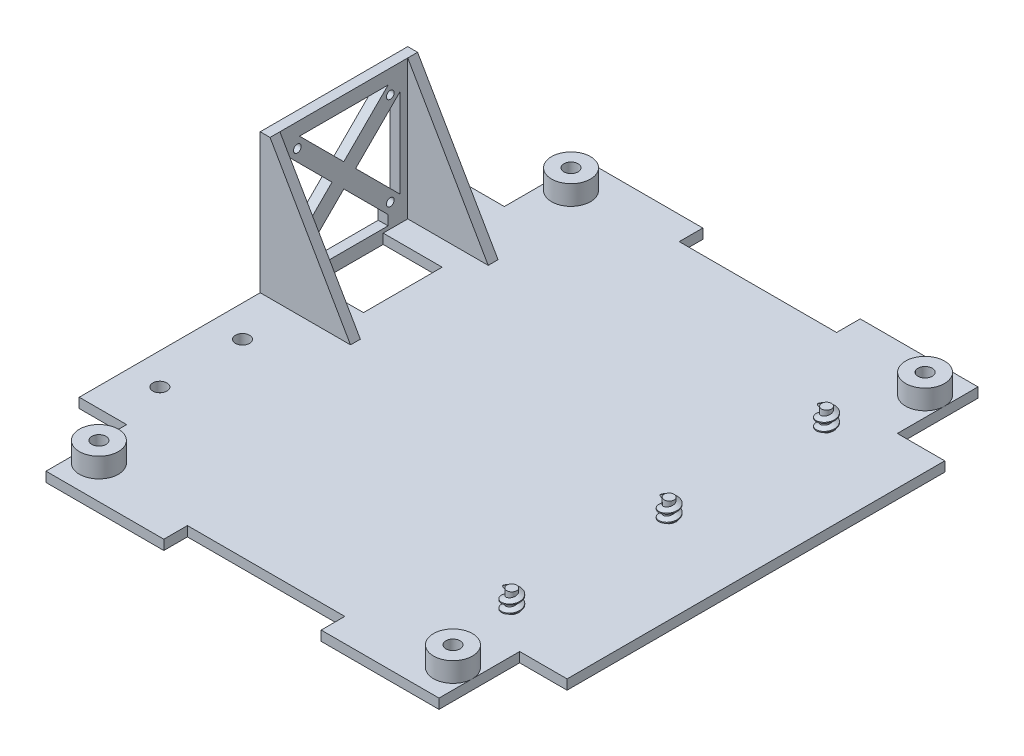
SolidWorks part; units mm, degrees
ref_plane "Front Plane" through (0, 0, 0) normal (0, 0, 1) x (1, 0, 0)
ref_plane "Top Plane" through (0, 0, 0) normal (0, 1, 0) x (1, 0, 0)
ref_plane "Right Plane" through (0, 0, 0) normal (1, 0, 0) x (0, 0, -1)
sketch "Sketch1" plane through (0, 0, 0) normal (0, 1, 0) x (1, 0, 0)
  line L0 (-25.4, 86.995) -> (-63.4314, 86.995)
  line L1 (-88.9, -101.6) -> (88.9, -101.6) construction
  line L2 (101.6, -88.9) -> (101.6, 88.9) construction
  line L3 (88.9, 101.6) -> (-88.9, 101.6) construction
  line L4 (-78.74, -60.96) -> (-63.4314, -60.96)
  line L5 (-63.4314, -60.96) -> (-63.4314, -86.995)
  line L6 (-63.4314, -86.995) -> (-25.4, -86.995)
  line L7 (63.4314, -86.995) -> (63.4314, -60.96)
  line L8 (63.4314, -60.96) -> (78.74, -60.96)
  line L9 (78.74, -60.96) -> (78.74, -25.4)
  line L10 (78.74, 60.96) -> (63.4314, 60.96)
  line L11 (63.4314, 60.96) -> (63.4314, 86.995)
  line L12 (63.4314, 86.995) -> (25.4, 86.995)
  line L13 (-63.4314, 86.995) -> (-63.4314, 60.96)
  line L14 (-63.4314, 60.96) -> (-78.74, 60.96)
  line L15 (-78.74, 60.96) -> (-78.74, 25.4)
  line L16 (-78.74, -25.4) -> (-78.74, -60.96)
  line L17 (-78.74, -25.4) -> (-71.12, -25.4)
  line L19 (-78.74, 25.4) -> (-71.12, 25.4)
  line L20 (-71.12, -25.4) -> (-71.12, 25.4)
  line L22 (-25.4, 86.995) -> (-25.4, 79.375)
  line L23 (-25.4, 79.375) -> (25.4, 79.375)
  line L24 (25.4, 86.995) -> (25.4, 79.375)
  line L25 (78.74, 25.4) -> (71.12, 25.4)
  line L27 (78.74, -25.4) -> (71.12, -25.4)
  line L28 (71.12, 25.4) -> (71.12, -25.4)
  line L30 (25.4, -86.995) -> (25.4, -79.375)
  line L31 (25.4, -79.375) -> (-25.4, -79.375)
  line L32 (-25.4, -86.995) -> (-25.4, -79.375)
  line L33 (78.74, 25.4) -> (78.74, 60.96)
  line L34 (25.4, -86.995) -> (63.4314, -86.995)
  line L35 (-101.6, 88.9) -> (-101.6, -88.9) construction
  arc A0 (88.9, -101.6) -> (101.6, -88.9) centre (88.9, -88.9) ccw construction
  arc A1 (-101.6, -88.9) -> (-88.9, -101.6) centre (-88.9, -88.9) ccw construction
  arc A2 (101.6, 88.9) -> (88.9, 101.6) centre (88.9, 88.9) ccw construction
  arc A3 (-101.6, 88.9) -> (-88.9, 101.6) centre (-88.9, 88.9) cw construction
  circle A4 centre (-57.15, 76.2) radius 2.286
  circle A5 centre (57.15, 76.2) radius 2.286
  circle A6 centre (57.15, -76.2) radius 2.286
  circle A7 centre (-57.15, -76.2) radius 2.286
  point P3 (0, 101.6)
  point P5 (101.6, 0)
  point P13 (101.6, 101.6)
  point P16 (-101.6, 101.6)
  point P38 (-71.12, 0)
  point P55 (0, -79.375)
  point P56 (0, 79.375)
  point P57 (71.12, 0)
  dimension "D2" = 12.7
  dimension "D11" = 4.572
  dimension "D8" = 44.45
  dimension "D1" = 203.2
  dimension "D3" = 203.2
  dimension "D4" = 22.86
  dimension "D5" = 15.3086
  dimension "D6" = 35.56
  dimension "D7" = 173.99
  dimension "D12" = 50.8
  dimension "D13" = 25.4
  dimension "D14" = 44.45
  dimension "D15" = 25.4
  dimension "D18" = 7.62
extrude "Main Body" add sketch "Sketch1" along normal blind 3.175
sketch "Sketch34" plane through (0, 3.175, 0) normal (0, 1, 0) x (1, 0, 0)
  line L0 (78.74, 25.4) -> (78.74, -25.4)
  line L1 (-78.74, 25.4) -> (-78.74, -25.4)
  line L28 (-78.74, -25.4) -> (-78.74, -60.96)
  line L29 (-78.74, -60.96) -> (-63.4314, -60.96)
  line L30 (-63.4314, -60.96) -> (-63.4314, -86.995)
  line L31 (-63.4314, -86.995) -> (-25.4, -86.995)
  line L32 (-25.4, -86.995) -> (-25.4, -79.375)
  line L33 (-25.4, -79.375) -> (25.4, -79.375)
  line L34 (25.4, -79.375) -> (25.4, -86.995)
  line L35 (25.4, -86.995) -> (63.4314, -86.995)
  line L36 (63.4314, -86.995) -> (63.4314, -60.96)
  line L37 (63.4314, -60.96) -> (78.74, -60.96)
  line L38 (78.74, -60.96) -> (78.74, -25.4)
  line L39 (78.74, -25.4) -> (71.12, -25.4)
  line L40 (71.12, -25.4) -> (71.12, 25.4)
  line L41 (71.12, 25.4) -> (78.74, 25.4)
  line L42 (78.74, 25.4) -> (78.74, 60.96)
  line L43 (78.74, 60.96) -> (63.4314, 60.96)
  line L44 (63.4314, 60.96) -> (63.4314, 86.995)
  line L45 (63.4314, 86.995) -> (25.4, 86.995)
  line L46 (25.4, 86.995) -> (25.4, 79.375)
  line L47 (25.4, 79.375) -> (-25.4, 79.375)
  line L48 (-25.4, 79.375) -> (-25.4, 86.995)
  line L49 (-25.4, 86.995) -> (-63.4314, 86.995)
  line L50 (-63.4314, 86.995) -> (-63.4314, 60.96)
  line L51 (-63.4314, 60.96) -> (-78.74, 60.96)
  line L52 (-78.74, 60.96) -> (-78.74, 25.4)
  line L53 (-78.74, 25.4) -> (-71.12, 25.4)
  line L54 (-71.12, 25.4) -> (-71.12, -25.4)
  line L55 (-71.12, -25.4) -> (-78.74, -25.4)
  line L56 (-78.74, -25.4) -> (-78.74, -60.96)
  line L57 (-78.74, -60.96) -> (-63.4314, -60.96)
  line L58 (-63.4314, -60.96) -> (-63.4314, -86.995)
  line L59 (-63.4314, -86.995) -> (-25.4, -86.995)
  line L60 (-25.4, -86.995) -> (-25.4, -79.375)
  line L61 (-25.4, -79.375) -> (25.4, -79.375)
  line L62 (25.4, -79.375) -> (25.4, -86.995)
  line L63 (25.4, -86.995) -> (63.4314, -86.995)
  line L64 (63.4314, -86.995) -> (63.4314, -60.96)
  line L65 (63.4314, -60.96) -> (78.74, -60.96)
  line L66 (78.74, -60.96) -> (78.74, -25.4)
  line L67 (78.74, -25.4) -> (71.12, -25.4)
  line L68 (71.12, -25.4) -> (71.12, 25.4)
  line L69 (71.12, 25.4) -> (78.74, 25.4)
  line L70 (78.74, 25.4) -> (78.74, 60.96)
  line L71 (78.74, 60.96) -> (63.4314, 60.96)
  line L72 (63.4314, 60.96) -> (63.4314, 86.995)
  line L73 (63.4314, 86.995) -> (25.4, 86.995)
  line L74 (25.4, 86.995) -> (25.4, 79.375)
  line L75 (25.4, 79.375) -> (-25.4, 79.375)
  line L76 (-25.4, 79.375) -> (-25.4, 86.995)
  line L77 (-25.4, 86.995) -> (-63.4314, 86.995)
  line L78 (-63.4314, 86.995) -> (-63.4314, 60.96)
  line L79 (-63.4314, 60.96) -> (-78.74, 60.96)
  line L80 (-78.74, 60.96) -> (-78.74, 25.4)
  line L81 (-78.74, 25.4) -> (-71.12, 25.4)
  line L82 (-71.12, 25.4) -> (-71.12, -25.4)
  line L83 (-71.12, -25.4) -> (-78.74, -25.4)
  line M42 (78.74, -25.4) -> (71.12, -25.4)
  line M43 (71.12, -25.4) -> (71.12, 25.4)
  line M44 (71.12, 25.4) -> (78.74, 25.4)
  line M56 (-78.74, 25.4) -> (-71.12, 25.4)
  line M57 (-71.12, 25.4) -> (-71.12, -25.4)
  line M58 (-71.12, -25.4) -> (-78.74, -25.4)
  dimension "D1" = 0
extrude "Boss-Extrude3" add sketch "Sketch34" against normal up to surface (3.175 mm away) contours L1 M56 M58 M57 | L0 M44 M43 M42 region at (74.93, 3.175, 0) region at (-74.93, 3.175, 0) up to face at (0, 0, 0)
sketch "Sketch3" plane through (0, 3.175, 0) normal (0, 1, 0) x (1, 0, 0)
  line L0 (50.7314, -50.8) -> (50.7314, 50.8) construction
  line L28 (-78.74, 60.96) -> (-78.74, -60.96)
  line L29 (-78.74, -60.96) -> (-63.4314, -60.96)
  line L30 (-63.4314, -60.96) -> (-63.4314, -86.995)
  line L31 (-63.4314, -86.995) -> (-25.4, -86.995)
  line L32 (-25.4, -86.995) -> (-25.4, -79.375)
  line L33 (-25.4, -79.375) -> (25.4, -79.375)
  line L34 (25.4, -79.375) -> (25.4, -86.995)
  line L35 (25.4, -86.995) -> (63.4314, -86.995)
  line L36 (63.4314, -86.995) -> (63.4314, -60.96)
  line L37 (63.4314, -60.96) -> (78.74, -60.96)
  line L38 (78.74, -60.96) -> (78.74, 60.96)
  line L43 (78.74, 60.96) -> (63.4314, 60.96)
  line L44 (63.4314, 60.96) -> (63.4314, 86.995)
  line L45 (63.4314, 86.995) -> (25.4, 86.995)
  line L46 (25.4, 86.995) -> (25.4, 79.375)
  line L47 (25.4, 79.375) -> (-25.4, 79.375)
  line L48 (-25.4, 79.375) -> (-25.4, 86.995)
  line L49 (-25.4, 86.995) -> (-63.4314, 86.995)
  line L50 (-63.4314, 86.995) -> (-63.4314, 60.96)
  line L51 (-63.4314, 60.96) -> (-78.74, 60.96)
  line L56 (-78.74, 60.96) -> (-78.74, -60.96)
  line L57 (-78.74, -60.96) -> (-63.4314, -60.96)
  line L58 (-63.4314, -60.96) -> (-63.4314, -86.995)
  line L59 (-63.4314, -86.995) -> (-25.4, -86.995)
  line L60 (-25.4, -86.995) -> (-25.4, -79.375)
  line L61 (-25.4, -79.375) -> (25.4, -79.375)
  line L62 (25.4, -79.375) -> (25.4, -86.995)
  line L63 (25.4, -86.995) -> (63.4314, -86.995)
  line L64 (63.4314, -86.995) -> (63.4314, -60.96)
  line L65 (63.4314, -60.96) -> (78.74, -60.96)
  line L66 (78.74, -60.96) -> (78.74, 60.96)
  line L71 (78.74, 60.96) -> (63.4314, 60.96)
  line L72 (63.4314, 60.96) -> (63.4314, 86.995)
  line L73 (63.4314, 86.995) -> (25.4, 86.995)
  line L74 (25.4, 86.995) -> (25.4, 79.375)
  line L75 (25.4, 79.375) -> (-25.4, 79.375)
  line L76 (-25.4, 79.375) -> (-25.4, 86.995)
  line L77 (-25.4, 86.995) -> (-63.4314, 86.995)
  line L78 (-63.4314, 86.995) -> (-63.4314, 60.96)
  line L79 (-63.4314, 60.96) -> (-78.74, 60.96)
  circle A0 centre (50.7314, 50.8) radius 1.5875
  circle A1 centre (50.7314, 0) radius 1.5875
  circle A2 centre (50.7314, -50.8) radius 1.5875
  dimension "D2" = 3.175
  dimension "D5" = 101.6
  dimension "D6" = 12.7
  dimension "D1" = 0
extrude "Boss-Extrude2" add sketch "Sketch3" along normal blind 6.35 contours A0 | A1 | A2
thread "Thread1" pitch 2.54 method extrude trim with end face yes profile "Thread Profile1" start angle 0, offset 0, length 0, pitch 2.54, diameter 3.175
ref_plane "Plane1" through (49.1439, 9.525, -50.8) normal (0, 0, 1) x (-1, 0, 0)
sketch "Thread Profile1" plane through (49.1439, 9.525, -50.8) normal (0, 0, 1) x (-1, 0, 0)
  line L0 (0, 0) -> (0, 2.54) construction
  line L1 (0, 0) -> (1.3748, 0.7937)
  line L2 (1.3748, 0.7937) -> (1.3748, 1.1112)
  line L3 (1.3748, 1.1112) -> (0, 1.905)
  line L4 (1.3748, 0.9525) -> (0, 0.9525) construction
  line L11 (0, 0) -> (0, 1.905)
  point P2 (0, 0)
  dimension "Pitch" = 2.54
  dimension "Profile_Angle" = 60
  dimension "Profile_Land" = 0.3175
  dimension "Profile_Height" = 1.3748
thread "Thread2" pitch 2.54 method extrude trim with end face yes profile "Thread Profile3" start angle 0, offset 0, length 0, pitch 2.54, diameter 3.175
ref_plane "Plane3" through (49.1439, 9.525, 0) normal (0, 0, 1) x (-1, 0, 0)
sketch "Thread Profile3" plane through (49.1439, 9.525, 0) normal (0, 0, 1) x (-1, 0, 0)
  line L0 (0, 0) -> (0, 2.54) construction
  line L1 (0, 0) -> (1.3748, 0.7937)
  line L2 (1.3748, 0.7937) -> (1.3748, 1.1112)
  line L3 (1.3748, 1.1112) -> (0, 1.905)
  line L4 (1.3748, 0.9525) -> (0, 0.9525) construction
  line L11 (0, 0) -> (0, 1.905)
  point P2 (0, 0)
  dimension "Pitch" = 2.54
  dimension "Profile_Angle" = 60
  dimension "Profile_Land" = 0.3175
  dimension "Profile_Height" = 1.3748
thread "Thread3" pitch 2.54 method extrude trim with end face yes profile "Thread Profile4" start angle 0, offset 0, length 0, pitch 2.54, diameter 3.175
ref_plane "Plane4" through (49.1439, 9.525, 50.8) normal (0, 0, 1) x (-1, 0, 0)
sketch "Thread Profile4" plane through (49.1439, 9.525, 50.8) normal (0, 0, 1) x (-1, 0, 0)
  line L0 (0, 0) -> (0, 2.54) construction
  line L1 (0, 0) -> (1.3748, 0.7937)
  line L2 (1.3748, 0.7937) -> (1.3748, 1.1112)
  line L3 (1.3748, 1.1112) -> (0, 1.905)
  line L4 (1.3748, 0.9525) -> (0, 0.9525) construction
  line L11 (0, 0) -> (0, 1.905)
  point P2 (0, 0)
  dimension "Pitch" = 2.54
  dimension "Profile_Angle" = 60
  dimension "Profile_Land" = 0.3175
  dimension "Profile_Height" = 1.3748
sketch "Sketch35" plane through (0, 3.175, 0) normal (0, 1, 0) x (1, 0, 0)
  line L20 (-78.74, 60.96) -> (-78.74, -60.96)
  line L21 (-78.74, -60.96) -> (-63.4314, -60.96)
  line L22 (-63.4314, -60.96) -> (-63.4314, -86.995)
  line L23 (-63.4314, -86.995) -> (-25.4, -86.995)
  line L24 (-25.4, -86.995) -> (-25.4, -79.375)
  line L25 (-25.4, -79.375) -> (25.4, -79.375)
  line L26 (25.4, -79.375) -> (25.4, -86.995)
  line L27 (25.4, -86.995) -> (63.4314, -86.995)
  line L28 (63.4314, -86.995) -> (63.4314, -60.96)
  line L29 (63.4314, -60.96) -> (78.74, -60.96)
  line L30 (78.74, -60.96) -> (78.74, 60.96)
  line L31 (78.74, 60.96) -> (63.4314, 60.96)
  line L32 (63.4314, 60.96) -> (63.4314, 86.995)
  line L33 (63.4314, 86.995) -> (25.4, 86.995)
  line L34 (25.4, 86.995) -> (25.4, 79.375)
  line L35 (25.4, 79.375) -> (-25.4, 79.375)
  line L36 (-25.4, 79.375) -> (-25.4, 86.995)
  line L37 (-25.4, 86.995) -> (-63.4314, 86.995)
  line L38 (-63.4314, 86.995) -> (-63.4314, 60.96)
  line L39 (-63.4314, 60.96) -> (-78.74, 60.96)
  line L40 (-78.74, 60.96) -> (-78.74, -60.96)
  line L41 (-78.74, -60.96) -> (-63.4314, -60.96)
  line L42 (-63.4314, -60.96) -> (-63.4314, -86.995)
  line L43 (-63.4314, -86.995) -> (-25.4, -86.995)
  line L44 (-25.4, -86.995) -> (-25.4, -79.375)
  line L45 (-25.4, -79.375) -> (25.4, -79.375)
  line L46 (25.4, -79.375) -> (25.4, -86.995)
  line L47 (25.4, -86.995) -> (63.4314, -86.995)
  line L48 (63.4314, -86.995) -> (63.4314, -60.96)
  line L49 (63.4314, -60.96) -> (78.74, -60.96)
  line L50 (78.74, -60.96) -> (78.74, 60.96)
  line L51 (78.74, 60.96) -> (63.4314, 60.96)
  line L52 (63.4314, 60.96) -> (63.4314, 86.995)
  line L53 (63.4314, 86.995) -> (25.4, 86.995)
  line L54 (25.4, 86.995) -> (25.4, 79.375)
  line L55 (25.4, 79.375) -> (-25.4, 79.375)
  line L56 (-25.4, 79.375) -> (-25.4, 86.995)
  line L57 (-25.4, 86.995) -> (-63.4314, 86.995)
  line L58 (-63.4314, 86.995) -> (-63.4314, 60.96)
  line L59 (-63.4314, 60.96) -> (-78.74, 60.96)
  circle A0 centre (-57.15, 76.2) radius 2.286 construction
  circle A1 centre (-57.15, -76.2) radius 2.286 construction
  circle A2 centre (57.15, -76.2) radius 2.286 construction
  circle A3 centre (57.15, 76.2) radius 2.286 construction
  circle A4 centre (-57.15, 76.2) radius 2.286
  circle A5 centre (-57.15, -76.2) radius 2.286
  circle A6 centre (57.15, -76.2) radius 2.286
  circle A7 centre (57.15, 76.2) radius 2.286
  circle A8 centre (-57.15, 76.2) radius 6.2814
  circle A9 centre (-57.15, -76.2) radius 6.2814
  circle A10 centre (57.15, -76.2) radius 6.2814
  circle A11 centre (57.15, 76.2) radius 6.2814
  circle M21 centre (57.15, -76.2) radius 2.286
  circle M22 centre (-57.15, 76.2) radius 2.286
  circle M43 centre (57.15, 76.2) radius 2.286
  circle M44 centre (-57.15, -76.2) radius 2.286
  dimension "D1" = 0
extrude "Boss-Extrude4" add sketch "Sketch35" along normal blind 6.35 contours A11 M43 | A10 M21 | A9 M44 | A8 M22 region at (-57.15, 3.175, 70.0962) region at (51.0462, 3.175, 76.2) region at (51.0462, 3.175, -76.2) region at (-57.15, 3.175, -82.3038)
sketch "Sketch36" plane through (0, 3.175, 0) normal (0, 1, 0) x (1, 0, 0)
  line L0 (-78.2696, -45.212) -> (-78.2696, -40.64)
  line L1 (-70.6496, -48.26) -> (-78.2696, -45.212)
  line L2 (-63.4314, 60.96) -> (-78.74, 60.96) construction
  line L3 (-78.74, 60.96) -> (-78.74, -60.96) construction
  line L4 (-78.74, -60.96) -> (-63.4314, -60.96) construction
  line L5 (-66.8396, -48.26) -> (-70.6496, -48.26)
  line L6 (-59.2196, -45.212) -> (-66.8396, -48.26)
  line L7 (-59.2196, -40.64) -> (-59.2196, -45.212)
  line L96 (-78.74, -60.96) -> (-63.4314, -60.96)
  line L97 (-78.74, 60.96) -> (-78.74, -60.96)
  line L98 (-63.4314, 60.96) -> (-78.74, 60.96)
  line L99 (-78.2696, -31.115) -> (-59.2196, -31.115) construction
  line L100 (-78.2696, -21.59) -> (-59.2196, -21.59)
  line L101 (-78.2696, -21.59) -> (-78.2696, -40.64)
  line L102 (-78.2696, -40.64) -> (-59.2196, -40.64)
  line L103 (-59.2196, -21.59) -> (-59.2196, -40.64)
  line L104 (-78.2696, -21.59) -> (-59.2196, -40.64) construction
  line L105 (-78.2696, -40.64) -> (-59.2196, -21.59) construction
  line L106 (-59.2196, -21.59) -> (-59.2196, -17.018)
  line L107 (-59.2196, -17.018) -> (-66.8396, -13.97)
  line L108 (-66.8396, -13.97) -> (-70.6496, -13.97)
  line L109 (-70.6496, -13.97) -> (-78.2696, -17.018)
  line L110 (-78.2696, -17.018) -> (-78.2696, -21.59)
  circle A0 centre (-68.7446, -17.78) radius 2.286
  circle A1 centre (-68.7446, -44.45) radius 2.286
  point P0 (-68.7446, -31.115)
  dimension "D6" = 4.572
  dimension "D1" = 19.05
  dimension "D2" = 4.572
  dimension "D3" = 7.62
  dimension "D4" = 3.81
  dimension "D5" = 3.81
  dimension "D7" = 12.7
  dimension "D8" = 0.4704
sketch "Sketch37" plane through (0, 3.175, 0) normal (0, 1, 0) x (1, 0, 0)
  line L2 (-63.4314, 60.96) -> (-78.74, 60.96) construction
  line L3 (-78.74, 60.96) -> (-78.74, -60.96) construction
  line L24 (-78.74, 60.96) -> (-78.74, -60.96)
  line L25 (-63.4314, 60.96) -> (-78.74, 60.96)
  line L27 (-78.74, 45.085) -> (-75.565, 45.085)
  line L28 (-78.74, 45.085) -> (-78.74, -2.54)
  line L29 (-78.74, -2.54) -> (-75.565, -2.54)
  line L30 (-75.565, 45.085) -> (-75.565, -2.54)
  dimension "D1" = 3.175
  dimension "D2" = 47.625
  dimension "D3" = 15.875
extrude "Boss-Extrude5" add sketch "Sketch37" along normal blind 45 contours L30 L27 L24 L29 region at (-77.1525, 3.175, -21.2725)
sketch "Sketch38" plane through (0, 0, -45.085) normal (0, 0, -1) x (-1, 0, 0)
  line L0 (75.565, 48.175) -> (49.5842, 3.175)
  line L1 (25.4, 3.175) -> (63.4314, 3.175) construction
  line L2 (49.5842, 3.175) -> (75.565, 3.175)
  line L4 (75.565, 3.175) -> (78.74, 3.175)
  line L5 (78.74, 3.175) -> (78.74, 48.175)
  line L6 (78.74, 48.175) -> (75.565, 48.175)
  line L7 (75.565, 48.175) -> (75.565, 3.175)
  line L8 (75.565, 3.175) -> (78.74, 3.175)
  line L9 (78.74, 3.175) -> (78.74, 48.175)
  line L10 (78.74, 48.175) -> (75.565, 48.175)
  line L11 (75.565, 48.175) -> (75.565, 3.175)
  line M9 (75.565, 48.175) -> (75.565, 3.175)
  dimension "D2" = 30
  dimension "D1" = 0
extrude "Boss-Extrude6" add sketch "Sketch38" against normal blind 3.175 contours L0 L2 M9 region at (-66.9047, 18.175, -45.085)
sketch "Sketch39" plane through (0, 0, 2.54) normal (0, 0, 1) x (1, 0, 0)
  line L0 (-75.565, 48.175) -> (-49.5842, 3.175)
  line L1 (-49.5842, 3.175) -> (-75.565, 3.175)
  line L4 (-78.74, 3.175) -> (-75.565, 3.175)
  line L5 (-75.565, 3.175) -> (-75.565, 48.175)
  line L6 (-75.565, 48.175) -> (-78.74, 48.175)
  line L7 (-78.74, 48.175) -> (-78.74, 3.175)
  line L8 (-78.74, 3.175) -> (-75.565, 3.175)
  line L9 (-75.565, 3.175) -> (-75.565, 48.175)
  line L10 (-75.565, 48.175) -> (-78.74, 48.175)
  line L11 (-78.74, 48.175) -> (-78.74, 3.175)
  line M7 (-75.565, 3.175) -> (-75.565, 48.175)
  dimension "D2" = 30
  dimension "D1" = 0
extrude "Boss-Extrude7" add sketch "Sketch39" against normal blind 3.175 contours L1 L0 M7 region at (-66.9047, 18.175, 2.54)
sketch "Sketch40" plane through (-78.74, 0, 0) normal (-1, 0, 0) x (0, 0, 1)
  line L0 (-35.56, 43.7725) -> (-6.985, 43.7725)
  line L1 (-40.2725, 6.675) -> (-2.2725, 6.675)
  line L2 (-40.2725, 6.675) -> (-40.2725, 44.675)
  line L3 (-40.2725, 44.675) -> (-2.2725, 44.675)
  line L4 (-2.2725, 6.675) -> (-2.2725, 44.675)
  line L5 (-40.2725, 6.675) -> (-2.2725, 44.675) construction
  line L6 (-40.2725, 44.675) -> (-2.2725, 6.675) construction
  line L7 (-6.985, 43.7725) -> (-21.2725, 29.485)
  line L8 (-60.96, 0) -> (60.96, 0)
  line L9 (60.96, 0) -> (60.96, 3.175)
  line L10 (60.96, 3.175) -> (2.54, 3.175)
  line L11 (2.54, 3.175) -> (2.54, 48.175)
  line L12 (2.54, 48.175) -> (-45.085, 48.175)
  line L13 (-45.085, 48.175) -> (-45.085, 3.175)
  line L14 (-45.085, 3.175) -> (-60.96, 3.175)
  line L15 (-60.96, 3.175) -> (-60.96, 0)
  line L16 (-60.96, 0) -> (60.96, 0)
  line L17 (60.96, 0) -> (60.96, 3.175)
  line L18 (60.96, 3.175) -> (2.54, 3.175)
  line L19 (2.54, 3.175) -> (2.54, 48.175)
  line L20 (2.54, 48.175) -> (-45.085, 48.175)
  line L21 (-45.085, 48.175) -> (-45.085, 3.175)
  line L22 (-45.085, 3.175) -> (-60.96, 3.175)
  line L23 (-60.96, 3.175) -> (-60.96, 0)
  line L24 (-21.2725, 29.485) -> (-35.56, 43.7725)
  line L25 (-17.4625, 25.675) -> (-3.175, 39.9625)
  line L26 (-3.175, 39.9625) -> (-3.175, 11.3875)
  line L27 (-3.175, 11.3875) -> (-17.4625, 25.675)
  line L28 (-21.2725, 21.865) -> (-6.985, 7.5775)
  line L29 (-6.985, 7.5775) -> (-35.56, 7.5775)
  line L30 (-35.56, 7.5775) -> (-21.2725, 21.865)
  line L31 (-25.0825, 25.675) -> (-39.37, 11.3875)
  line L32 (-39.37, 11.3875) -> (-39.37, 39.9625)
  line L33 (-39.37, 39.9625) -> (-25.0825, 25.675)
  circle A0 centre (-36.2725, 40.675) radius 1.25
  circle A1 centre (-6.2725, 40.675) radius 1.25
  circle A2 centre (-6.2725, 10.675) radius 1.25
  circle A3 centre (-36.2725, 10.675) radius 1.25
  point P2 (-45.085, 25.675)
  point P4 (-21.2725, 48.175)
  point P6 (-21.2725, 25.675)
  point P15 (-6.2725, 40.675)
  point P16 (-6.2725, 10.675)
  point P17 (-36.2725, 40.675)
  point P18 (-36.2725, 10.675)
  point P29 (-21.2725, 43.7725)
  point P43 (-21.2725, 25.675)
  dimension "D4" = 2.5
  dimension "D2" = 38
  dimension "D3" = 4
  dimension "D5" = 28.575
  dimension "D6" = 3.81
  dimension "D7" = 45
  dimension "D8" = 4
  dimension "D1" = 0
extrude "Cut-Extrude3" cut sketch "Sketch40" against normal up to surface (3.175 mm away) contours L25 L26 L27 | L28 L29 L30 | A2 | A3 | L31 L32 L33 | L7 L24 L0 | A1 | A0 up to face at (-75.565, 25.675, -21.2725)
sketch "Sketch41" plane through (0, 3.175, 0) normal (0, 1, 0) x (1, 0, 0)
  line L0 (-75.565, 41.91) -> (-75.565, 0.635) construction
  line L31 (-49.5842, 41.91) -> (-75.565, 41.91) construction
  line L32 (-49.5842, 0.635) -> (-75.565, 0.635) construction
  line L33 (-49.5842, 0.635) -> (-75.565, 0.635)
  line L34 (-75.565, 41.91) -> (-75.565, 0.635)
  line L35 (-49.5842, 41.91) -> (-75.565, 41.91)
  line L37 (-75.565, 8.5725) -> (-56.515, 8.5725)
  line L38 (-75.565, 8.5725) -> (-75.565, 33.9725)
  line L39 (-75.565, 33.9725) -> (-56.515, 33.9725)
  line L40 (-56.515, 8.5725) -> (-56.515, 33.9725)
  point P7 (-75.565, 21.2725)
  point P8 (-56.515, 21.2725)
  dimension "D1" = 19.05
  dimension "D2" = 25.4
extrude "Cut-Extrude4" cut sketch "Sketch41" against normal up to next contours L37 L40 L39 L34 region at (-66.04, 3.175, -21.2725)
sketch "Sketch48" plane through (-78.74, 0, 0) normal (-1, 0, 0) x (0, 0, 1)
  line L0 (-6.985, 7.5775) -> (-35.56, 7.5775) construction
  line L1 (-6.985, 7.5775) -> (-35.56, 7.5775)
  line L2 (-35.56, 7.5775) -> (-35.56, 4.4025)
  line L3 (-35.56, 4.4025) -> (-6.985, 4.4025)
  line L4 (-6.985, 4.4025) -> (-6.985, 7.5775)
  line L12 (-60.96, 0) -> (60.96, 0)
  line L13 (60.96, 0) -> (60.96, 3.175)
  line L14 (60.96, 3.175) -> (2.54, 3.175)
  line L19 (2.54, 3.175) -> (2.54, 48.175)
  line L20 (2.54, 48.175) -> (-45.085, 48.175)
  line L21 (-45.085, 48.175) -> (-45.085, 3.175)
  line L22 (-45.085, 3.175) -> (-60.96, 3.175)
  line L23 (-60.96, 3.175) -> (-60.96, 0)
  line L24 (-60.96, 0) -> (60.96, 0)
  line L25 (60.96, 0) -> (60.96, 3.175)
  line L26 (60.96, 3.175) -> (2.54, 3.175)
  line L31 (2.54, 3.175) -> (2.54, 48.175)
  line L32 (2.54, 48.175) -> (-45.085, 48.175)
  line L33 (-45.085, 48.175) -> (-45.085, 3.175)
  line L34 (-45.085, 3.175) -> (-60.96, 3.175)
  line L35 (-60.96, 3.175) -> (-60.96, 0)
  line M19 (-6.985, 7.5775) -> (-35.56, 7.5775)
  dimension "D2" = 3.175
  dimension "D1" = 0
extrude "Cut-Extrude6" cut sketch "Sketch48" against normal up to next contours L3 L4 L2 M19 region at (-78.74, 5.99, -21.2725)
sketch "Sketch49" plane through (0, 3.175, 0) normal (0, 1, 0) x (1, 0, 0)
  line L0 (-68.58, -18.415) -> (-68.58, -45.085) construction
  line L1 (-78.74, -2.54) -> (-78.74, -60.96) construction
  circle A0 centre (-68.58, -18.415) radius 2.286
  circle A1 centre (-68.58, -45.085) radius 2.286
  point P4 (-68.58, -31.75)
  point P7 (-78.74, -31.75)
  dimension "D1" = 4.572
  dimension "D2" = 26.67
  dimension "D3" = 10.16
extrude "Cut-Extrude7" cut sketch "Sketch49" against normal through all
